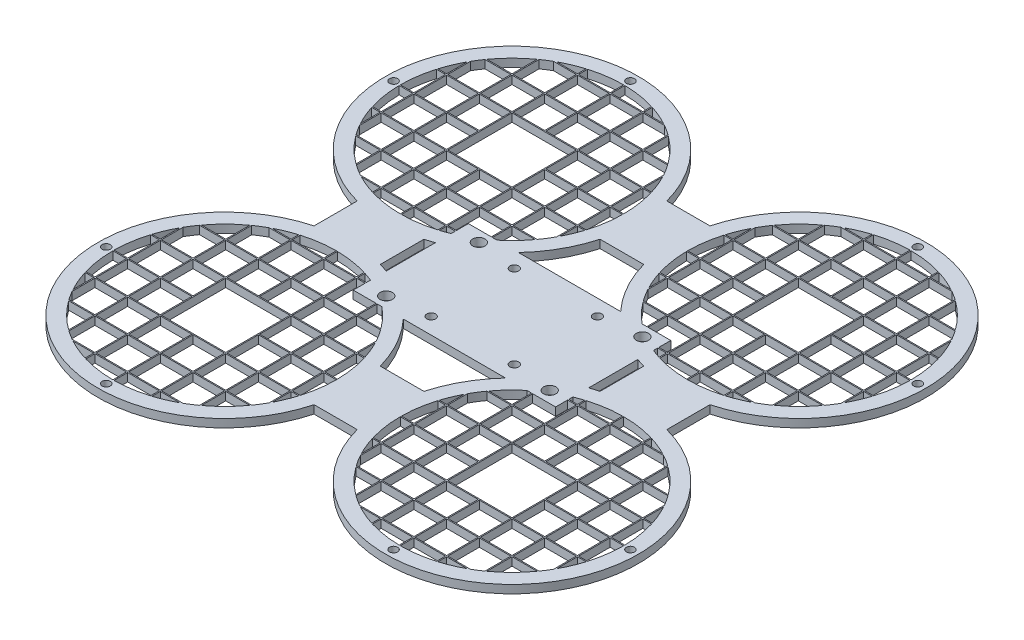
SolidWorks part; units mm, degrees
ref_plane "Front Plane" through (0, 0, 0) normal (0, 0, 1) x (1, 0, 0)
ref_plane "Top Plane" through (0, 0, 0) normal (0, 1, 0) x (1, 0, 0)
ref_plane "Right Plane" through (0, 0, 0) normal (1, 0, 0) x (0, 0, -1)
sketch "Sketch2" plane through (0, 0, 0) normal (0, 1, 0) x (1, 0, 0)
  circle A1 centre (0, 0) radius 41
  circle A2 centre (0, 0) radius 46
  point P208 (0, 0)
extrude "Boss-Extrude2" add sketch "Sketch2" along normal blind 3
sketch "Sketch4" plane through (0, 3, 0) normal (0, 1, 0) x (1, 0, 0)
  line L0 (0, 46) -> (0, 12)
  line L1 (12, 44.4072) -> (12, -44.4072)
  line L2 (24, 39.2428) -> (24, -39.2428)
  line L3 (36, 28.6356) -> (36, -28.6356)
  line L4 (-12, 44.4072) -> (-12, -44.4072)
  line L5 (-24, 39.2428) -> (-24, -32)
  line L6 (-36, 28.6356) -> (-36, -28.6356)
  line L7 (-46, 0) -> (-12, 0)
  line L8 (-44.4072, -12) -> (44.4072, -12)
  line L9 (-39.2428, -24) -> (39.2428, -24)
  line L10 (12, 0) -> (46, 0)
  line L11 (-44.4072, 12) -> (44.4072, 12)
  line L12 (-39.2428, 24) -> (39.2428, 24)
  line L13 (-28.6356, 36) -> (28.6356, 36)
  line L14 (-16, -36) -> (28.6356, -36)
  line L15 (0, -12) -> (0, -46)
  line L50 (-26.0661, -32) -> (-16, -32)
  line L52 (-26.0661, -32) -> (-26.0661, -37.902)
  line L60 (-16, -32) -> (-16, -43.1277)
  line L61 (-28.6356, -36) -> (-26.0661, -36) [skipped]
  circle A1 centre (0, 0) radius 46 construction
  circle A2 centre (0, 0) radius 46
  dimension "D1" = 4
  dimension "D2" = 4
extrude "Extrude-Thin5" add sketch "Sketch4" against normal blind 3 thin thin type one direction wall 0.4
sketch "Sketch5" plane through (0, 0, 0) normal (0, -1, 0) x (1, 0, 0)
  circle A0 centre (0, -43.4524) radius 1.5
  circle A3 centre (43.4524, 0) radius 1.5
  circle A4 centre (0, 43.4524) radius 1.5 [skipped]
  circle A5 centre (-43.4524, 0) radius 1.5 [skipped]
  point P11 (0, 0)
  dimension "D1" = 4
extrude "Cut-Extrude1" cut sketch "Sketch5" against normal blind 3
sketch "Sketch8" plane through (0, 3, 0) normal (0, 1, 0) x (1, 0, 0)
  line L1 (-16, -32) -> (-25.632, -32)
  line L2 (-16, -32) -> (-16, -37.7492)
  line L3 (-16, -37.7492) -> (-25.632, -37.7492)
  line L4 (-25.632, -32) -> (-25.632, -37.7492)
extrude "Boss-Extrude4" add sketch "Sketch8" against normal through all
sketch "Sketch9" plane through (0, 3, 0) normal (0, 1, 0) x (1, 0, 0)
  circle A3 centre (-22.2697, -36.1812) radius 2.25
extrude "Cut-Extrude3" cut sketch "Sketch9" against normal through all
ref_plane "Plane1" through (-52.73, 0, 0) normal (1, 0, 0) x (0, 0, -1)
mirror "Mirror1" about plane through (-52.73, 0, 0) normal (1, 0, 0) of bodies 159
sketch "Sketch10" plane through (0, 3, 0) normal (0, 1, 0) x (1, 0, 0)
  line L0 (-66.2554, 12) -> (-69.06, 12) construction
  line L1 (-63.5152, 12) -> (-41.7915, 12)
  line L2 (-63.5152, 12) -> (-63.5152, -12.4)
  line L3 (-63.5152, -12.4) -> (-41.7915, -12.4)
  line L4 (-41.7915, 12) -> (-41.7915, -12.4)
  line L5 (-66.3801, -12.4) -> (-69.06, -12.4) construction
extrude "Boss-Extrude5" add sketch "Sketch10" against normal up to surface (3 mm away) up to face at (-22.2697, 0, 38.4312)
ref_plane "Plane2" through (0, 0, 52.73) normal (0, 0, 1) x (1, 0, 0)
mirror "Mirror2" about plane through (0, 0, 52.73) normal (0, 0, 1) of bodies 177
sketch "Sketch11" plane through (0, 3, 0) normal (0, 1, 0) x (1, 0, 0)
  line L0 (-93.06, -36.4) -> (-93.06, -39.0799) construction
  line L1 (-117.46, -41.6571) -> (-93.06, -41.6571)
  line L2 (-117.46, -41.6571) -> (-117.46, -63.409)
  line L3 (-117.46, -63.409) -> (-93.06, -63.409)
  line L4 (-93.06, -41.6571) -> (-93.06, -63.409)
  line L5 (-117.46, -36.4) -> (-117.46, -39.2046) construction
extrude "Boss-Extrude6" add sketch "Sketch11" against normal up to surface (3 mm away) up to face at (-52.73, 0, -0.0036)
sketch "Sketch12" plane through (0, 3, 0) normal (0, 1, 0) x (1, 0, 0)
  line L0 (12, -36.4) -> (12, -39.2046) construction
  line L1 (-12.4, -42.0227) -> (12, -42.0227)
  line L2 (-12.4, -42.0227) -> (-12.4, -63.5098)
  line L3 (-12.4, -63.5098) -> (12, -63.5098)
  line L4 (12, -42.0227) -> (12, -63.5098)
  line L5 (-12.4, -36.4) -> (-12.4, -39.0799) construction
extrude "Boss-Extrude7" add sketch "Sketch12" against normal up to surface (3 mm away) up to face at (-62.5401, 0, 52.73)
sketch "Sketch13" plane through (0, 0, 0) normal (0, -1, 0) x (1, 0, 0)
  line L1 (-89.86, 73.86) -> (-15.6, 73.86)
  line L2 (-89.86, 73.86) -> (-89.86, 31.6)
  line L3 (-89.86, 31.6) -> (-15.6, 31.6)
  line L4 (-15.6, 73.86) -> (-15.6, 31.6)
extrude "Boss-Extrude8" add sketch "Sketch13" against normal up to surface (3 mm away) up to face at (-52.73, 3, 52.73)
sketch "Sketch15" plane through (0, 0, 0) normal (0, -1, 0) x (1, 0, 0)
  circle A0 centre (-36.702, 37.4126) radius 1.6 construction
  circle A1 centre (-67.202, 37.4124) radius 1.6 construction
  circle A2 centre (-67.2022, 67.9124) radius 1.6 construction
  circle A3 centre (-36.7022, 67.9126) radius 1.6 construction
  circle A4 centre (-36.702, 37.4126) radius 1.6
  circle A5 centre (-67.202, 37.4124) radius 1.6
  circle A6 centre (-67.2022, 67.9124) radius 1.6
  circle A7 centre (-36.7022, 67.9126) radius 1.6
extrude "Cut-Extrude5" cut sketch "Sketch15" against normal up to next
ref_plane "Plane3" through (-32.452, 23.8804, 37.4126) normal (0, 0, 1) x (1, 0, 0)
ref_plane "Plane4" through (-43.3021, 7.6858, 53.1026) normal (0, 0, 1) x (1, 0, 0)
sketch "Sketch18" plane through (0, 0, 0) normal (0, -1, 0) x (1, 0, 0)
  circle A0 centre (-21.9522, 69.6627) radius 2.25 construction
  circle A1 centre (-21.952, 35.6627) radius 2.25 construction
  circle A2 centre (-81.952, 35.6623) radius 2.25 construction
  circle A3 centre (-81.9522, 69.6623) radius 2.25 construction
  circle A4 centre (-21.9522, 69.6627) radius 2.25
  circle A5 centre (-21.952, 35.6627) radius 2.25
  circle A6 centre (-81.952, 35.6623) radius 2.25
  circle A7 centre (-81.9522, 69.6623) radius 2.25
extrude "Cut-Extrude6" cut sketch "Sketch18" against normal up to next
